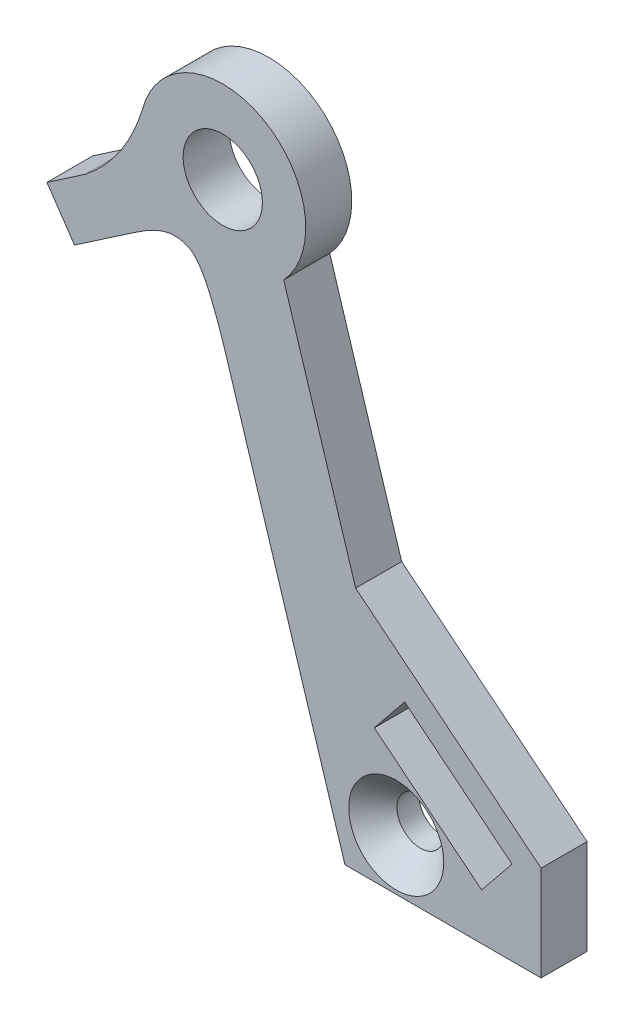
SolidWorks part; units mm, degrees
ref_plane "Front Plane" through (0, 0, 0) normal (0, 0, 1) x (1, 0, 0)
ref_plane "Top Plane" through (0, 0, 0) normal (0, 1, 0) x (1, 0, 0)
ref_plane "Right Plane" through (0, 0, 0) normal (1, 0, 0) x (0, 0, -1)
sketch "Sketch1" plane through (0, 0, 0) normal (0, 0, 1) x (1, 0, 0)
  line L0 (0, 10.5) -> (13, 0) construction
  line L1 (0, 0) -> (13, 0)
  line L2 (0, 0) -> (0, 10.5) construction
  line L3 (0, 10.5) -> (13, 10.5) construction
  line L4 (13, 0) -> (13, 10.5) construction
  line L5 (0, 0) -> (3.4, 0)
  line L6 (0, 0) -> (0, 3.4)
  line L7 (0, 3.4) -> (3.4, 3.4) construction
  line L8 (3.4, 0) -> (3.4, 3.4) construction
  line L9 (9.0068, 3.1288) -> (9.054, 3.1872) construction
  line L10 (9.0632, 3.0833) -> (1.945, 8.8326)
  line L11 (1.945, 8.8326) -> (3.9557, 11.322)
  line L12 (9.0632, 3.0833) -> (11.0738, 5.5728)
  line L13 (3.9557, 11.322) -> (11.0738, 5.5728)
  line L14 (0, 0) -> (-10.7241, 34.4576)
  line L15 (-10.7241, 34.4576) -> (-5.4725, 36.092)
  line L16 (-5.4725, 36.092) -> (0.7085, 16.2316)
  line L17 (0.7085, 16.2316) -> (13, 6.3039)
  line L18 (13, 0) -> (9.1103, 3.1417)
  line L19 (13, 6.3039) -> (13, 0)
  line L20 (0, 0) -> (0, 43.2357) construction
  line L21 (-8.0983, 35.2748) -> (-18.8392, 27.9513) construction
  line L22 (-17.9237, 26.6087) -> (-19.7546, 29.2939)
  line L23 (-19.7546, 29.2939) -> (-13.3551, 33.6574) construction
  line L24 (-17.9237, 26.6087) -> (-11.5242, 30.9721)
  line L25 (-19.7546, 29.2939) -> (-17.2295, 31.0156)
  line L26 (-13.4277, 36.6338) -> (-8.0983, 35.2748) construction
  circle A0 centre (3.4, 3.4) radius 1.5
  circle A1 centre (-8.0983, 35.2748) radius 2.625
  circle A3 centre (-8.0983, 35.2748) radius 5.5
  spline S0 degree 2 poles (-17.2295, 31.0156) (-14.5142, 33.1421) (-13.4277, 36.6338) knots 0 0 0 1 1 1
  spline S1 degree 3 poles (-13.9328, 29.3299) (-12.3816, 30.4078) (-10.6916, 30.7893) (-9.2236, 29.6097) (-7.8132, 25.1048) knots 0 0 0 0 0.517104 1 1 1 1
  point P28 (-18.8392, 27.9513)
  point P32 (0, 43.2357)
  dimension "D5" = 3
  dimension "D6" = 5.25
  dimension "D7" = 11
  dimension "D26" = 6.892
  dimension "D1" = 13
  dimension "D2" = 10.5
  dimension "D3" = 3.4
  dimension "D4" = 3.4
  dimension "D8" = 51.072
  dimension "D9" = 6.3039
  dimension "D10" = 90
  dimension "D11" = 90
  dimension "D12" = 20.8
  dimension "D13" = 15.8
  dimension "D14" = 3.2
  dimension "D15" = 9.15
  dimension "D16" = 0.075
  dimension "D17" = 5
  dimension "D18" = 5.5
  dimension "D19" = 90
  dimension "D20" = 3.25
  dimension "D21" = 90
  dimension "D22" = 90
  dimension "D23" = 13
  dimension "D24" = 73
  dimension "D25" = 3.0562
  dimension "D27" = 31.593
extrude "Boss-Extrude1" add sketch "Sketch1" along normal blind 3.05 contours A3 S1 L14 L15 A1 L16 S0 | L14 A3 L16 L15 A1 | A3 L14 L1 L12 L10 L11 L13 L19 L17 L16 A0 | S0 L25 L22 L24 A3 | L24 S1 A3 | A3 S1 L14 region at (0.8388, 12.7884, 0) region at (-9.2169, 29.0135, 0) region at (-9.8194, 30.2141, 0) region at (-7.0451, 31.8908, 0) region at (-11.7561, 30.5152, 0) region at (-15.5674, 30.4807, 0)
hole_wizard "CSK for M3 Flat Head Machine Screw1" positions "Sketch2" profile "Sketch3" countersink size "M3" standard "ANSI Metric" end condition through all
sketch "Sketch2" plane through (0, 0, 3.05) normal (0, 0, 1) x (1, 0, 0)
  point P0 (3.4, 3.4)
sketch "Sketch3" plane through (3.4, 3.4, 3.05) normal (1, 0, 0) x (0, -1, 0)
  line L0 (0, 0) -> (0, 3.05)
  line L1 (0, 3.05) -> (1.55, 3.05)
  line L2 (1.55, 3.05) -> (1.55, 1.6)
  line L3 (1.55, 1.6) -> (3.15, 0)
  line L5 (3.15, 0) -> (0, 0)
  line L6 (-1.55, 1.6) -> (-3.15, 0) construction
  line L11 (0, -6.35) -> (0, 107.95) construction
  dimension "Thru Hole Dia." = 3.1
  dimension "Thru Hole Depth" = 3.05
  dimension "Near C'Sink Dia." = 6.3
  dimension "Near C'Sink Angle" = 90
